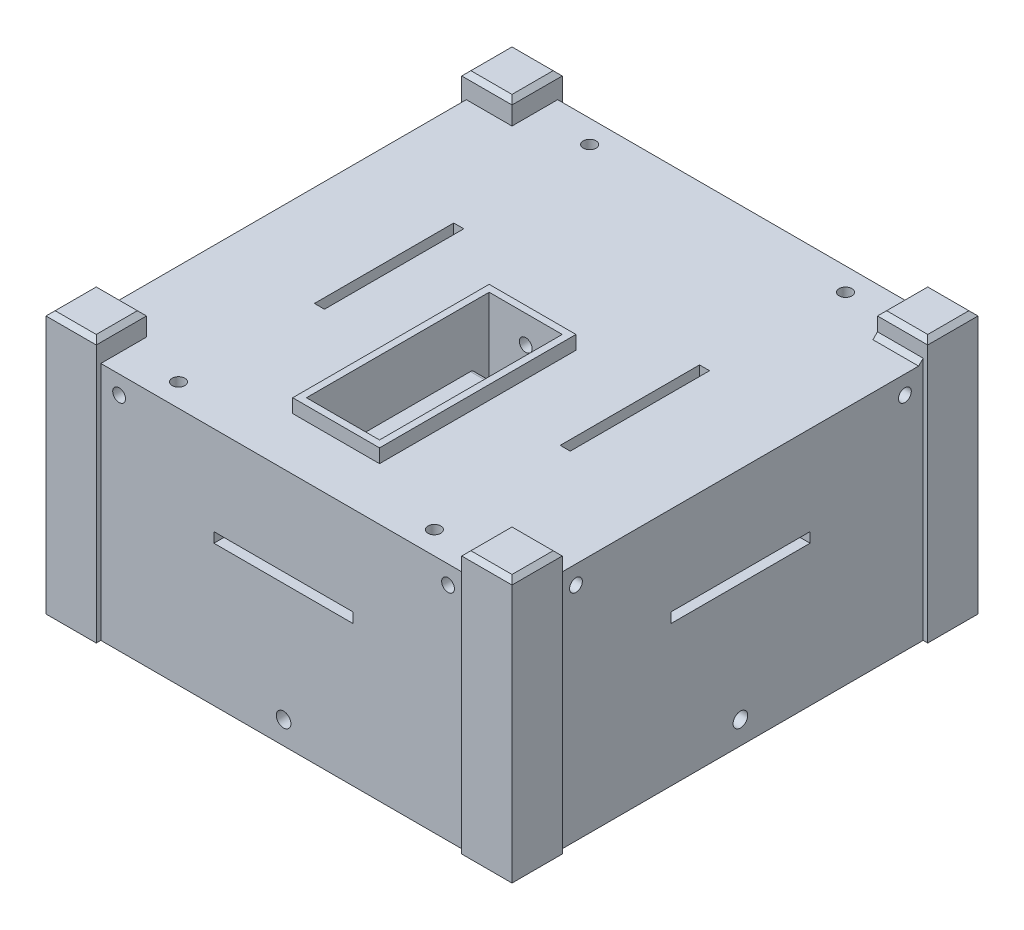
SolidWorks part; units mm, degrees
ref_plane "Front Plane" through (0, 0, 0) normal (0, 0, 1) x (1, 0, 0)
ref_plane "Top Plane" through (0, 0, 0) normal (0, 1, 0) x (1, 0, 0)
ref_plane "Right Plane" through (0, 0, 0) normal (1, 0, 0) x (0, 0, -1)
sketch "Sketch1" plane through (0, 0, 0) normal (0, 1, 0) x (1, 0, 0)
  line L1 (-50, 50) -> (50, 50)
  line L2 (-50, 50) -> (-50, -50)
  line L3 (-50, -50) -> (50, -50)
  line L4 (50, 50) -> (50, -50)
  line L5 (-50, 50) -> (50, -50) construction
  line L6 (-50, -50) -> (50, 50) construction
  point P0 (0, 0)
  dimension "D1" = 100
  dimension "D2" = 100
extrude "Boss-Extrude1" add sketch "Sketch1" along normal blind 95
ref_plane "Plane1" through (0, 100, 0) normal (0, 1, 0) x (1, 0, 0)
sketch "Sketch2" plane through (0, 100, 0) normal (0, 1, 0) x (1, 0, 0)
  line L0 (0, 0) -> (0, 71.0273) construction
  line L1 (-50, 50) -> (-40, 50)
  line L2 (-50, 50) -> (-50, 40)
  line L3 (-50, 40) -> (-40, 40)
  line L4 (-40, 50) -> (-40, 40)
  line L5 (50, 40) -> (40, 40)
  line L6 (40, 50) -> (40, 40)
  line L7 (50, 50) -> (40, 50)
  line L8 (50, 50) -> (50, 40)
  line L9 (0, 0) -> (-74.2097, 0) construction
  line L10 (50, -50) -> (50, -40)
  line L11 (50, -50) -> (40, -50)
  line L12 (40, -50) -> (40, -40)
  line L13 (50, -40) -> (40, -40)
  line L14 (-50, -40) -> (-40, -40)
  line L15 (-40, -50) -> (-40, -40)
  line L16 (-50, -50) -> (-40, -50)
  line L17 (-50, -50) -> (-50, -40)
  dimension "D1" = 10
  dimension "D2" = 10
extrude "Boss-Extrude2" add sketch "Sketch2" against normal blind 105
sketch "Sketch3" plane through (0, 95, 0) normal (0, 1, 0) x (1, 0, 0)
  line L0 (0, 0) -> (-55.4811, 0) construction
  line L1 (0, 0) -> (0, -56.887) construction
  line L3 (50, -40) -> (40, -40) construction
  circle A0 centre (-28, -45) radius 1.4
  circle A1 centre (28, -45) radius 1.4
  circle A2 centre (28, 45) radius 1.4
  circle A3 centre (-28, 45) radius 1.4
  dimension "D1" = 2.8
  dimension "D2" = 28
  dimension "D3" = 85
extrude "Cut-Extrude1" cut sketch "Sketch3" against normal blind 10
sketch "Sketch4" plane through (0, 100, 0) normal (0, 1, 0) x (1, 0, 0)
  line L0 (-50, 50) -> (-50, 40) construction
  line L1 (-40, 40) -> (-51, 40)
  line L2 (-40, 40) -> (-40, 51)
  line L3 (-40, 51) -> (-51, 51)
  line L4 (-51, 40) -> (-51, 51)
  line L5 (40, 50) -> (-40, 50) construction
  line L6 (0, 0) -> (0, 60.0537) construction
  line L7 (0, 0) -> (-61.4769, 0) construction
  line L8 (40, 51) -> (51, 51)
  line L9 (51, 40) -> (51, 51)
  line L10 (40, 40) -> (51, 40)
  line L11 (40, 40) -> (40, 51)
  line L12 (40, -40) -> (40, -51)
  line L13 (40, -40) -> (51, -40)
  line L14 (51, -40) -> (51, -51)
  line L15 (40, -51) -> (51, -51)
  line L16 (-40, -51) -> (-51, -51)
  line L17 (-51, -40) -> (-51, -51)
  line L18 (-40, -40) -> (-51, -40)
  line L19 (-40, -40) -> (-40, -51)
  dimension "D1" = 1
  dimension "D2" = 1
extrude "Boss-Extrude3" add sketch "Sketch4" against normal up to surface (105 mm away) up to face at (-45, -5, -45)
sketch "Sketch5" plane through (0, 0, 50) normal (0, 0, 1) x (1, 0, 0)
  line L0 (0, 95) -> (0, 43.7031) construction
  line L1 (-40, 95) -> (40, 95) construction
  line L2 (40, 47.5) -> (-59.8843, 47.5) construction
  line L3 (40, 0) -> (40, 95) construction
  line L4 (-40, 95) -> (-40, 0) construction
  circle A0 centre (-36, 91) radius 1.4
  circle A1 centre (36, 91) radius 1.4
  circle A2 centre (36, 4) radius 1.4
  circle A3 centre (-36, 4) radius 1.4
  dimension "D1" = 2.8
  dimension "D2" = 4
  dimension "D3" = 4
extrude "Cut-Extrude2" cut sketch "Sketch5" against normal blind 10
mirror "Mirror1" about plane through (0, 0, 0) normal (0, 0, 1) of "Cut-Extrude2"
sketch "Sketch6" plane through (-50, 0, 0) normal (-1, 0, 0) x (0, 0, 1)
  line L0 (-40, 95) -> (-40, 0) construction
  line L1 (-40, 95) -> (40, 95) construction
  line L2 (0, 95) -> (0, 40.4022) construction
  line L3 (-40, 47.5) -> (36.0105, 47.5) construction
  line L4 (-40, -5) -> (-40, 100) construction
  circle A0 centre (-36, 91) radius 1.4
  circle A1 centre (36, 91) radius 1.4
  circle A2 centre (36, 4) radius 1.4
  circle A3 centre (-36, 4) radius 1.4
  dimension "D1" = 2.8
  dimension "D2" = 4
  dimension "D3" = 4
extrude "Cut-Extrude3" cut sketch "Sketch6" against normal blind 10
mirror "Mirror2" about plane through (0, 0, 0) normal (1, 0, 0) of "Cut-Extrude3"
ref_plane "Plane2" through (0, 47.5, 0) normal (0, 1, 0) x (1, 0, 0)
mirror "Mirror3" about plane through (0, 47.5, 0) normal (0, 1, 0) of "Cut-Extrude1"
chamfer "Chamfer1" distance 1 angle 45 33 edges at (-45.5, -5, 51) (-40, -5, 45.5) (-45.5, -5, 40) (-51, -5, 45.5) (40, -5, 45.5) (45.5, -5, 51) (51, -5, 45.5) (45.5, -5, 40) (45.5, -5, -51) (40, -5, -45.5) (45.5, -5, -40) (51, -5, -45.5) (-40, -5, -45.5) (-45.5, -5, -51) (-51, -5, -45.5) (-45.5, -5, -40) (45.5, 100, 51) (40, 100, 45.5) (45.5, 100, 40) (51, 100, 45.5) (40, 100, -45.5) (45.5, 100, -51) (51, 100, -45.5) (45.5, 100, -40) (-45.5, 100, -40) (-51, 100, -45.5) (-45.5, 100, -51) (-40, 100, -45.5) (-40, 100, 45.5) (-45.5, 100, 51) (-51, 100, 45.5) (-45.5, 100, 40) (45, 95, -40)
sketch "Sketch7" plane through (0, 95, 0) normal (0, 1, 0) x (1, 0, 0)
  line L0 (9.5, 4.5) -> (9.5, -38.5)
  line L1 (-8, 3) -> (8, 3)
  line L2 (-8, 3) -> (-8, -37)
  line L3 (-8, -37) -> (8, -37)
  line L4 (8, 3) -> (8, -37)
  line L5 (-9.5, -38.5) -> (9.5, -38.5)
  line L6 (-9.5, 4.5) -> (-9.5, -38.5)
  line L7 (-9.5, 4.5) -> (9.5, 4.5)
  dimension "D1" = 8
  dimension "D2" = 8
  dimension "D3" = 3
  dimension "D4" = 40
  dimension "D5" = 1.5
extrude "Boss-Extrude4" add sketch "Sketch7" along normal blind 3
sketch "Sketch8" plane through (0, 95, 0) normal (0, 1, 0) x (1, 0, 0)
  line L4 (-8, 3) -> (-8, -37)
  line L5 (-8, -37) -> (8, -37)
  line L6 (8, -37) -> (8, 3)
  line L7 (8, 3) -> (-8, 3)
  line L8 (-8, 3) -> (-8, -37)
  line L9 (-8, -37) -> (8, -37)
  line L10 (8, -37) -> (8, 3)
  line L11 (8, 3) -> (-8, 3)
  dimension "D1" = 0
extrude "Cut-Extrude4" cut sketch "Sketch8" against normal blind 10
chamfer "Chamfer2" distance 13 angle 45 1 edges at (0, 85, 37)
sketch "Sketch9" plane through (0, 85, 0) normal (0, 1, 0) x (1, 0, 0)
  line L0 (8, -24) -> (8, 3) construction
  line L1 (-8, 3) -> (8, 3)
  line L2 (-8, 3) -> (-8, -0.1)
  line L3 (-8, -0.1) -> (8, -0.1)
  line L4 (8, 3) -> (8, -0.1)
  dimension "D1" = 3.1
extrude "Cut-Extrude5" cut sketch "Sketch9" against normal blind 10
fillet "Fillet1" radius 1 1 edges at (0, 85, 0.1)
sketch "Sketch10" plane through (0, 0, -3) normal (0, 0, 1) x (1, 0, 0)
  line L0 (8, 98) -> (-8, 98) construction
  line L1 (-8, 98) -> (-8, 75) construction
  circle A0 centre (0, 92) radius 1.4
  dimension "D1" = 2.8
  dimension "D2" = 6
  dimension "D3" = 8
extrude "Cut-Extrude6" cut sketch "Sketch10" against normal blind 10
sketch "Sketch11" plane through (0, 0, 0) normal (0, -1, 0) x (1, 0, 0)
  line L0 (-50, -40) -> (-50, 40) construction
  circle A0 centre (0, -15) radius 5
  dimension "D1" = 10
  dimension "D2" = 15
  dimension "D3" = 50
extrude "Boss-Extrude5" add sketch "Sketch11" along normal blind 3
sketch "Sketch12" plane through (-50, 0, 0) normal (-1, 0, 0) x (0, 0, 1)
  line L0 (-40, 95) -> (40, 95) construction
  line L1 (-15.25, 75.5) -> (15.25, 75.5)
  line L2 (-15.25, 75.5) -> (-15.25, 73.3)
  line L3 (-15.25, 73.3) -> (15.25, 73.3)
  line L4 (15.25, 75.5) -> (15.25, 73.3)
  line L5 (-15.25, 75.5) -> (15.25, 73.3) construction
  line L6 (-15.25, 73.3) -> (15.25, 75.5) construction
  line L7 (0, 95) -> (0, 60.126) construction
  line L8 (-51, 47.5) -> (62.2361, 47.5) construction
  line L9 (-51, -4) -> (-51, 99) construction
  line L10 (-15.25, 21.7) -> (15.25, 21.7)
  line L11 (15.25, 19.5) -> (15.25, 21.7)
  line L12 (-15.25, 19.5) -> (15.25, 19.5)
  line L13 (-15.25, 19.5) -> (-15.25, 21.7)
  line L14 (-40, 0) -> (40, 0) construction
  point P0 (0, 74.4)
  dimension "D1" = 19.5
  dimension "D2" = 2.2
  dimension "D3" = 30.5
extrude "Cut-Extrude7" cut sketch "Sketch12" against normal blind 3
mirror "Mirror4" about plane through (0, 0, 0) normal (1, 0, 0) of "Cut-Extrude7"
sketch "Sketch13" plane through (0, 0, 50) normal (0, 0, 1) x (1, 0, 0)
  line L0 (0, 95) -> (0, 46.2553) construction
  line L1 (-40, 95) -> (40, 95) construction
  line L2 (-51, 47.5) -> (61.8656, 47.5) construction
  line L3 (-15.25, 75.5) -> (15.25, 75.5)
  line L4 (-15.25, 75.5) -> (-15.25, 73.3)
  line L5 (-15.25, 73.3) -> (15.25, 73.3)
  line L6 (15.25, 75.5) -> (15.25, 73.3)
  line L7 (-15.25, 75.5) -> (15.25, 73.3) construction
  line L8 (-15.25, 73.3) -> (15.25, 75.5) construction
  line L9 (-51, -4) -> (-51, 99) construction
  line L10 (-15.25, 21.7) -> (15.25, 21.7)
  line L11 (15.25, 19.5) -> (15.25, 21.7)
  line L12 (-15.25, 19.5) -> (15.25, 19.5)
  line L13 (-15.25, 19.5) -> (-15.25, 21.7)
  point P5 (0, 74.4)
  dimension "D1" = 30.5
  dimension "D2" = 2.2
  dimension "D3" = 19.5
extrude "Cut-Extrude8" cut sketch "Sketch13" against normal blind 3
mirror "Mirror5" about plane through (0, 0, 0) normal (0, 0, 1) of "Cut-Extrude8"
sketch "Sketch14" plane through (0, 95, 0) normal (0, 1, 0) x (1, 0, 0)
  line L0 (-50, 0) -> (73.3052, 0) construction
  line L1 (-50, 40) -> (-50, -40) construction
  line L2 (0, 50) -> (0, -6.1969) construction
  line L3 (40, 50) -> (-40, 50) construction
  line L4 (28, 15.25) -> (25.8, 15.25)
  line L5 (-28, -15.25) -> (-25.8, -15.25)
  line L6 (-28, -15.25) -> (-28, 15.25)
  line L7 (-28, 15.25) -> (-25.8, 15.25)
  line L8 (-25.8, -15.25) -> (-25.8, 15.25)
  line L9 (-28, -15.25) -> (-25.8, 15.25) construction
  line L10 (-28, 15.25) -> (-25.8, -15.25) construction
  line L11 (25.8, -15.25) -> (25.8, 15.25)
  line L12 (28, -15.25) -> (25.8, -15.25)
  line L13 (28, -15.25) -> (28, 15.25)
  point P9 (-26.9, 0)
  dimension "D1" = 30.5
  dimension "D2" = 2.2
  dimension "D3" = 22
extrude "Cut-Extrude9" cut sketch "Sketch14" against normal blind 3
mirror "Mirror6" about plane through (0, 47.5, 0) normal (0, 1, 0) of "Cut-Extrude9"
sketch "Sketch15" plane through (0, 0, 0) normal (1, 0, 0) x (0, 0, -1)
  line L0 (-40, 0) -> (40, 0) construction
  line L1 (-45, 70) -> (45, 70)
  line L2 (-45, 70) -> (-45, 12)
  line L3 (-45, 12) -> (45, 12)
  line L4 (45, 70) -> (45, 12)
  line L5 (-45, 70) -> (45, 12) construction
  line L6 (-45, 12) -> (45, 70) construction
  line L7 (-51, -4) -> (-51, 99) construction
  line L8 (51, -4) -> (51, 99) construction
  line L9 (-40, 95) -> (39, 95) construction
  point P0 (0, 41)
  dimension "D1" = 12
  dimension "D2" = 6
  dimension "D3" = 6
  dimension "D4" = 25
extrude "Cut-Extrude10" cut sketch "Sketch15" against normal offset from surface 6 and the other way offset from surface 6 up to face at (-51, 47.5, -45.5) other way up to face at (51, 47.5, 45.5)
sketch "Sketch16" plane through (0, 0, 0) normal (0, 0, 1) x (1, 0, 0)
  line L0 (45, 57.0064) -> (-45, 57.0064)
  line L1 (51, -4) -> (51, 99) construction
  line L2 (-51, -4) -> (-51, 99) construction
  line L3 (45, 57.0064) -> (45, 83)
  line L4 (45, 83) -> (13, 83)
  line L5 (13, 83) -> (13, 67.0064)
  line L6 (13, 67.0064) -> (-13, 67.0064)
  line L7 (-13, 67.0064) -> (-13, 83)
  line L8 (-13, 83) -> (-45, 83)
  line L9 (-45, 83) -> (-45, 57.0064)
  line L10 (-40, 95) -> (40, 95) construction
  dimension "D1" = 6
  dimension "D2" = 6
  dimension "D3" = 57.0064
  dimension "D4" = 12
  dimension "D5" = 32
  dimension "D7" = 10
extrude "Cut-Extrude11" cut sketch "Sketch16" along normal up to surface and the other way up to surface up to face at (0, 41, 45) other way up to face at (0, 41, -45)
chamfer "Chamfer3" distance 4 angle 45 2 edges at (-13, 70, 0) (13, 70, 0)
sketch "Sketch17" plane through (51, 0, 0) normal (1, 0, 0) x (0, 0, -1)
  line L0 (-51, -4) -> (-51, 99) construction
  line L2 (-51, 42.5) -> (-51, -10.5351)
  line L3 (-51, -10.5351) -> (51, -10.5351)
  line L4 (51, 42.5) -> (51, -10.5351)
  line L5 (40, -4) -> (40, 99) construction
  line L6 (40, -4) -> (51, -4) construction
  line L7 (-51, 42.5) -> (51, 42.5)
  dimension "D1" = 11
  dimension "D2" = 6.5351
  dimension "D3" = 46.5
extrude "Cut-Extrude12" cut sketch "Sketch17" against normal through all
sketch "Sketch19" plane through (0, 42.5, 0) normal (0, -1, 0) x (1, 0, 0)
  line L1 (-47.5, 47.5) -> (47.5, 47.5)
  line L2 (-47.5, 47.5) -> (-47.5, -47.5)
  line L3 (-47.5, -47.5) -> (47.5, -47.5)
  line L4 (47.5, 47.5) -> (47.5, -47.5)
  line L5 (-47.5, 47.5) -> (47.5, -47.5) construction
  line L6 (-47.5, -47.5) -> (47.5, 47.5) construction
  point P0 (0, 0)
  dimension "D1" = 95
  dimension "D2" = 95
extrude "Cut-Extrude14" cut sketch "Sketch19" against normal blind 12
sketch "Sketch20" plane through (50, 0, 0) normal (1, 0, 0) x (0, 0, -1)
  line L0 (-40, 42.5) -> (40, 42.5) construction
  line L1 (-40, 95) -> (-40, 42.5) construction
  circle A0 centre (0, 47.5) radius 1.6
  dimension "D2" = 3.2
  dimension "D1" = 5
  dimension "D3" = 40
extrude "Cut-Extrude15" cut sketch "Sketch20" against normal through all
sketch "Sketch21" plane through (0, 0, -50) normal (0, 0, -1) x (-1, 0, 0)
  line L0 (-40, 42.5) -> (40, 42.5) construction
  line L1 (40, 42.5) -> (40, 95) construction
  circle A0 centre (0, 47.5) radius 1.6
  dimension "D1" = 3.2
  dimension "D2" = 5
  dimension "D3" = 40
extrude "Cut-Extrude16" cut sketch "Sketch21" against normal through all
